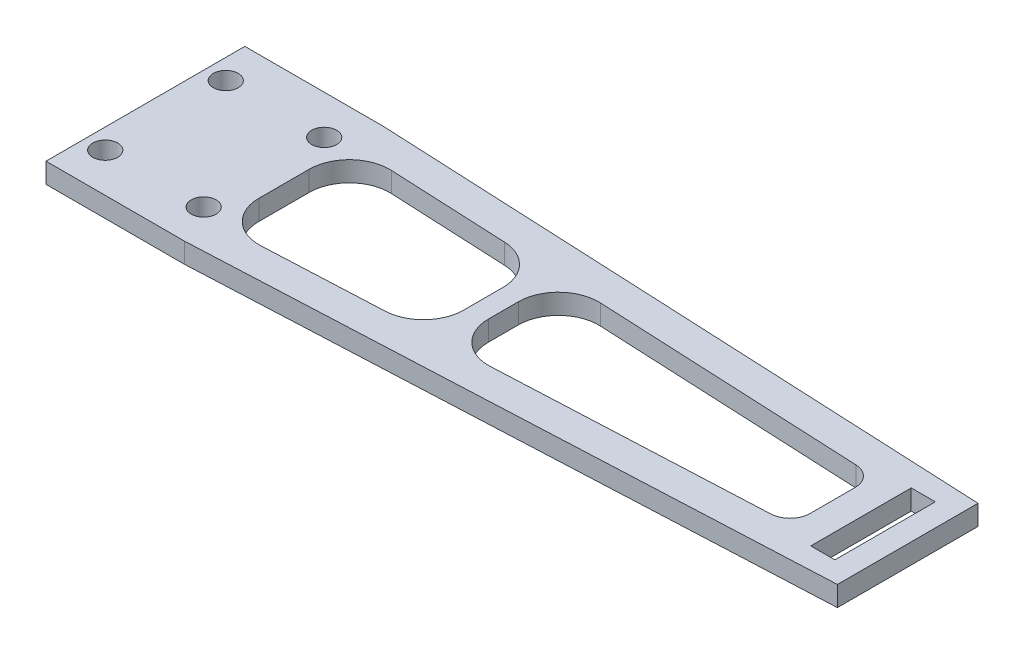
SolidWorks part; units mm, degrees
ref_plane "Front Plane" through (0, 0, 0) normal (0, 0, 1) x (1, 0, 0)
ref_plane "Top Plane" through (0, 0, 0) normal (0, 1, 0) x (1, 0, 0)
ref_plane "Right Plane" through (0, 0, 0) normal (1, 0, 0) x (0, 0, -1)
sketch "Sketch1" plane through (0, 0, 0) normal (0, 1, 0) x (1, 0, 0)
  line L1 (0, 0) -> (34.5, 0)
  line L2 (0, 0) -> (0, 49.5)
  line L3 (0, 49.5) -> (34.5, 49.5)
  line L4 (34.5, 0) -> (34.5, 49.5)
  dimension "D1" = 34.5
  dimension "D2" = 49.5
extrude "Boss-Extrude1" add sketch "Sketch1" along normal blind 5
sketch "Sketch2" plane through (0, 5, 0) normal (0, 1, 0) x (1, 0, 0)
  line L0 (34.5, 49.5) -> (0, 49.5) construction
  line L1 (0, 49.5) -> (0, 0) construction
  line L2 (17.25, 49.5) -> (17.25, 0) construction
  line L3 (0, 0) -> (34.5, 0) construction
  line L4 (0, 24.75) -> (17.25, 24.75) construction
  circle A0 centre (5, 39.75) radius 3.1
  circle A1 centre (5, 9.75) radius 3.1
  circle A2 centre (29.5, 9.75) radius 3.1
  circle A3 centre (29.5, 39.75) radius 3.1
  dimension "D1" = 6.2
  dimension "D3" = 5
  dimension "D2" = 9.75
extrude "Cut-Extrude1" cut sketch "Sketch2" against normal blind 5
sketch "Sketch3" plane through (0, 5, 0) normal (0, 1, 0) x (1, 0, 0)
  line L0 (17.25, 24.75) -> (181.75, 24.75) construction
  line L1 (189.75, 42.25) -> (34.5, 49.5)
  line L2 (189.75, 7.25) -> (34.5, 0)
  line L3 (189.75, 42.25) -> (189.75, 7.25)
  line L4 (171.0535, 14.3856) -> (89.0949, 10.5582)
  line L6 (171.0535, 35.1144) -> (89.0949, 38.9418)
  line L7 (34.5, 49.5) -> (34.5, 41.4913)
  line L8 (34.5, 0) -> (34.5, 49.5) construction
  line L9 (181.75, 34.6149) -> (34.1268, 41.5087) construction
  line L10 (34.5, 0) -> (34.5, 8.0087)
  line L11 (181.75, 14.8851) -> (34.1268, 7.9913) construction
  line L12 (84.0949, 39.1753) -> (84.0949, 10.3247)
  line L13 (89.0949, 38.9418) -> (89.0949, 10.5582)
  line L14 (89.0949, 39.1753) -> (89.0949, 10.3247) construction
  line L16 (0, 49.5) -> (0, 0) construction
  line L17 (0, 0) -> (34.5, 0) construction
  line L18 (84.0949, 39.1753) -> (34.5, 41.4913)
  line L19 (84.0949, 10.3247) -> (34.5, 8.0087)
  line L20 (171.0535, 35.1144) -> (171.0535, 14.3856)
  line L21 (181.75, 34.6149) -> (181.75, 14.8851) construction
  line L22 (178.13, 37.25) -> (184.13, 37.25)
  line L23 (178.13, 37.25) -> (178.13, 12.25)
  line L24 (178.13, 12.25) -> (184.13, 12.25)
  line L25 (184.13, 37.25) -> (184.13, 12.25)
  dimension "D1" = 17.5
  dimension "D4" = 17.25
  dimension "D5" = 24.75
  dimension "D6" = 17.5
  dimension "D7" = 172.5
  dimension "D8" = 25
  dimension "D9" = 12.5
  dimension "D10" = 6
  dimension "D11" = 5.62
  dimension "D2" = 8
  dimension "D3" = 5
extrude "Boss-Extrude2" add sketch "Sketch3" against normal blind 5
sketch "Sketch5" [suppressed] plane through (0, 5, 0) normal (0, 1, 0) x (1, 0, 0)
  line L0 (163.183, 43.1642) -> (163.183, 6.3358)
  line L1 (181.75, 42.25) -> (34.5, 49.5) construction
  line L2 (34.5, 0) -> (181.75, 7.25) construction
  line L3 (163.183, 6.3358) -> (181.75, 7.25)
  line L4 (181.75, 7.25) -> (181.75, 42.25)
  line L5 (181.75, 42.25) -> (163.183, 43.1642)
fillet "Fillet1" radius 10 6 edges at (89.0949, 2.5, -10.5582) (89.0949, 2.5, -38.9418) (84.0949, 2.5, -10.3247) (84.0949, 2.5, -39.1753) (34.5, 2.5, -41.4913) (34.5, 2.5, -8.0087)
fillet "Fillet2" radius 5 2 edges at (171.0535, 2.5, -14.3856) (171.0535, 2.5, -35.1144)
